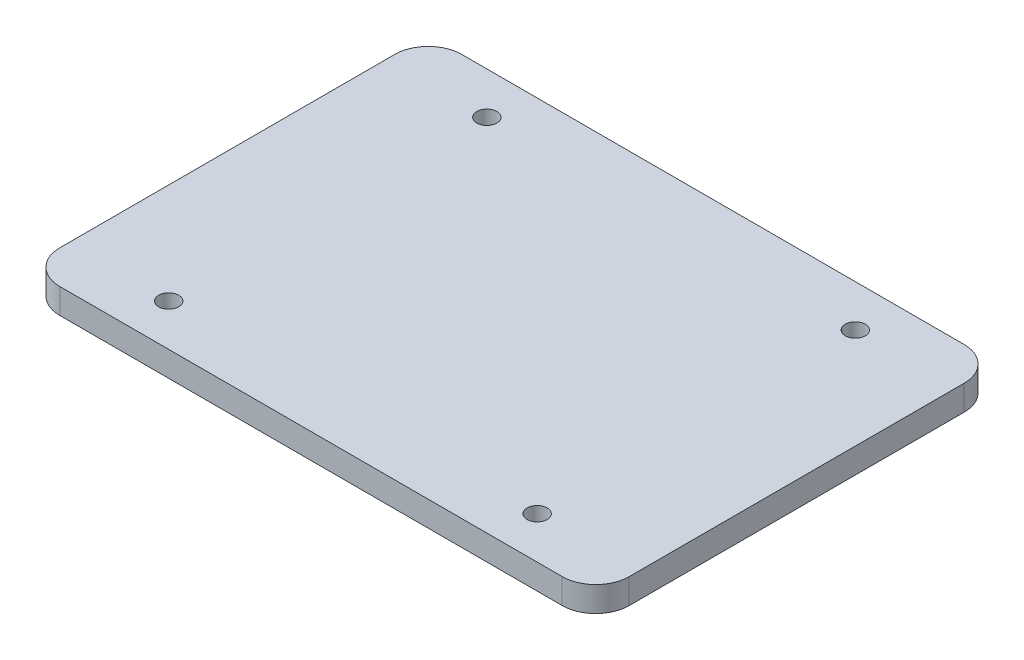
SolidWorks part; units mm, degrees
material "槭木"
ref_plane "前视基准面" through (0, 0, 0) normal (0, 0, 1) x (1, 0, 0)
ref_plane "上视基准面" through (0, 0, 0) normal (0, 1, 0) x (1, 0, 0)
ref_plane "右视基准面" through (0, 0, 0) normal (1, 0, 0) x (0, 0, -1)
other "Configuration Table"
sketch "草图2" plane through (0, 0, 0) normal (0, 1, 0) x (1, 0, 0)
  line L0 (0, 120) -> (0, -120) construction
  line L1 (-150, 120) -> (150, 120)
  line L2 (-170, 100) -> (-170, -100)
  line L3 (-150, -120) -> (150, -120)
  line L4 (170, 100) -> (170, -100)
  line L5 (-170, 120) -> (170, -120) construction
  line L6 (-170, -120) -> (170, 120) construction
  line L7 (-170, 0) -> (170, 0) construction
  line L9 (-170, 120) -> (-110, 120)
  line L10 (-170, 120) -> (-170, 95)
  line L11 (-170, 95) -> (-110, 95)
  line L12 (-110, 120) -> (-110, 95)
  arc A0 (-170, 100) -> (-150, 120) centre (-150, 100) cw
  arc A1 (-150, -120) -> (-170, -100) centre (-150, -100) cw
  arc A2 (150, -120) -> (170, -100) centre (150, -100) ccw
  arc A3 (170, 100) -> (150, 120) centre (150, 100) ccw
  circle A4 centre (-110, 95) radius 6
  circle A5 centre (-110, -95) radius 6
  circle A6 centre (110, -95) radius 6
  circle A7 centre (110, 95) radius 6
  point P0 (0, 0)
  dimension "D3" = 20
  dimension "D4" = 20
  dimension "D7" = 190
  dimension "D1" = 340
  dimension "D2" = 240
  dimension "D5" = 25
  dimension "D6" = 60
extrude "凸台-拉伸1" add sketch "草图2" along normal blind 15 contours L2 A1 L3 A2 L4 A3 L1 A0
extrude "切除-拉伸10" cut sketch "草图2<10>" along normal blind 15 contours A5
sketch "草图2<10>" plane through (0, 0, 0) normal (0, 1, 0) x (1, 0, 0) same geometry as "草图2"
extrude "切除-拉伸11" cut sketch "草图2<11>" along normal blind 15 contours A6
sketch "草图2<11>" plane through (0, 0, 0) normal (0, 1, 0) x (1, 0, 0) same geometry as "草图2"
extrude "切除-拉伸12" cut sketch "草图2<12>" along normal blind 15 contours A4
sketch "草图2<12>" plane through (0, 0, 0) normal (0, 1, 0) x (1, 0, 0) same geometry as "草图2"
extrude "切除-拉伸13" cut sketch "草图2<13>" along normal blind 15 contours A7
sketch "草图2<13>" plane through (0, 0, 0) normal (0, 1, 0) x (1, 0, 0) same geometry as "草图2"
